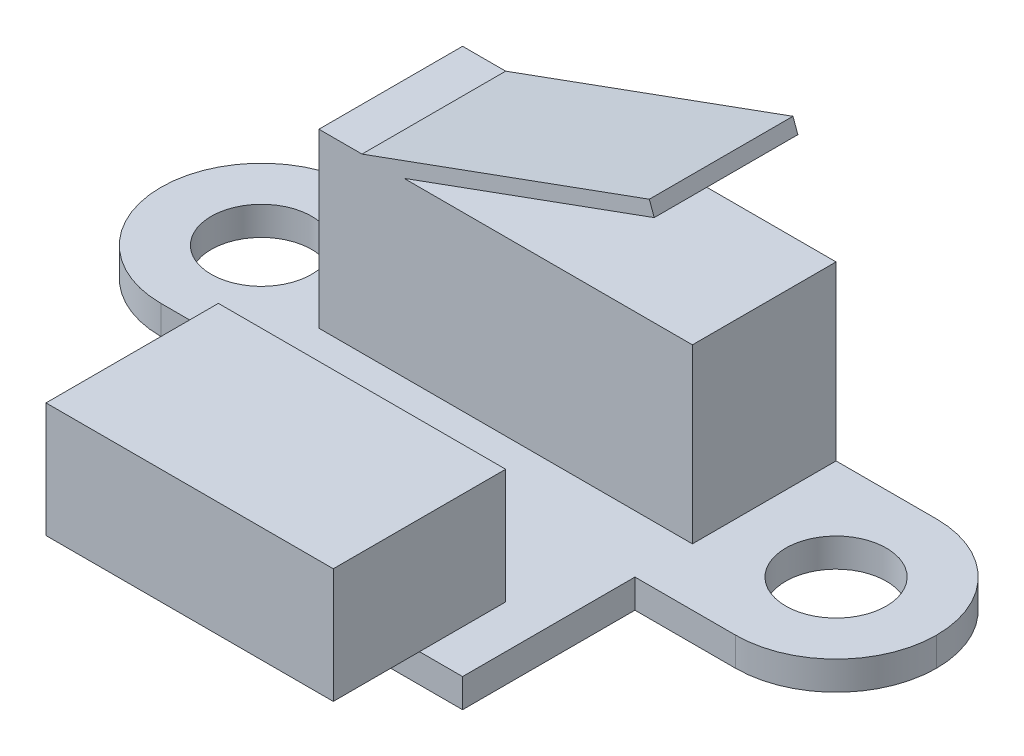
SolidWorks part; units mm, degrees
ref_plane "Front Plane" through (0, 0, 0) normal (0, 0, 1) x (1, 0, 0)
ref_plane "Top Plane" through (0, 0, 0) normal (0, 1, 0) x (1, 0, 0)
ref_plane "Right Plane" through (0, 0, 0) normal (1, 0, 0) x (0, 0, -1)
sketch "Sketch1" plane through (0, 0, 0) normal (0, 1, 0) x (1, 0, 0)
  line L1 (-6.5, -6.5) -> (6.5, -6.5)
  line L2 (-6.5, -6.5) -> (-6.5, 6.5)
  line L3 (-6.5, 6.5) -> (6.5, 6.5)
  line L4 (6.5, -6.5) -> (6.5, 6.5)
  line L5 (-6.5, -6.5) -> (6.5, 6.5) construction
  line L6 (-6.5, 6.5) -> (6.5, -6.5) construction
  point P0 (0, 0)
  dimension "D1" = 13
  dimension "D2" = 13
extrude "Boss-Extrude1" add sketch "Sketch1" along normal blind 1
sketch "Sketch4" plane through (-6.5, 0, 0) normal (-1, 0, 0) x (0, 0, 1)
  line L0 (-6.5, 1) -> (6.5, 1) construction
  line L1 (-6.5, 0) -> (0.5, 0)
  line L2 (-6.5, 0) -> (-6.5, 1)
  line L3 (-6.5, 1) -> (0.5, 1)
  line L4 (0.5, 0) -> (0.5, 1)
  dimension "D1" = 7
extrude "Boss-Extrude2" add sketch "Sketch4" along normal blind 7
sketch "Sketch5" plane through (6.5, 0, 0) normal (1, 0, 0) x (0, 0, -1)
  line L0 (-6.5, 0) -> (6.5, 0) construction
  line L1 (6.5, 1) -> (-0.5, 1)
  line L2 (6.5, 1) -> (6.5, 0)
  line L3 (6.5, 0) -> (-0.5, 0)
  line L4 (-0.5, 1) -> (-0.5, 0)
  dimension "D1" = 7
extrude "Boss-Extrude3" add sketch "Sketch5" along normal blind 7
sketch "Sketch6" plane through (0, 1, 0) normal (0, 1, 0) x (1, 0, 0)
  line L0 (-13.5, -0.5) -> (-6.5, -0.5) construction
  line L2 (-13.5, -0.5) -> (-13.5, 6.5) construction
  circle A0 centre (-10, 3) radius 1.75
  circle A1 centre (10, 3) radius 1.75
  dimension "D1" = 3.5
  dimension "D4" = 3.5
  dimension "D2" = 3.5
  dimension "D3" = 3.5
  dimension "D5" = 20
extrude "Cut-Extrude1" cut sketch "Sketch6" against normal through all
sketch "Sketch7" plane through (0, 1, 0) normal (0, 1, 0) x (1, 0, 0)
  line L0 (13.5, 6.5) -> (-13.5, 6.5) construction
  line L1 (-5, -3.5) -> (5, -3.5)
  line L2 (-5, -3.5) -> (-5, -9.5)
  line L3 (-5, -9.5) -> (5, -9.5)
  line L4 (5, -3.5) -> (5, -9.5)
  line L5 (-6.5, -0.5) -> (-6.5, -6.5) construction
  dimension "D1" = 6
  dimension "D2" = 10
  dimension "D3" = 10
  dimension "D4" = 1.5
extrude "Boss-Extrude4" add sketch "Sketch7" along normal blind 4
sketch "Sketch8" plane through (0, 1, 0) normal (0, 1, 0) x (1, 0, 0)
  line L0 (-6.5, -0.5) -> (-6.5, -6.5) construction
  line L1 (-6.5, 1.5) -> (6.5, 1.5)
  line L2 (-6.5, 1.5) -> (-6.5, 6.5)
  line L3 (-6.5, 6.5) -> (6.5, 6.5)
  line L4 (6.5, 1.5) -> (6.5, 6.5)
  line L5 (13.5, 6.5) -> (-13.5, 6.5) construction
  dimension "D1" = 13
  dimension "D2" = 0
  dimension "D3" = 5
  dimension "D4" = 0
extrude "Boss-Extrude5" add sketch "Sketch8" along normal blind 6
sketch "Sketch9" plane through (0, 0, -1.5) normal (0, 0, 1) x (1, 0, 0)
  line L0 (-5, 7) -> (5, 10.6397)
  line L1 (-6.5, 7) -> (6.5, 7) construction
  line L2 (-6.5, 7) -> (-6.5, 1) construction
  line L3 (5, 10.6397) -> (5.171, 10.1699)
  line L4 (5.171, 10.1699) -> (-3.5381, 7)
  line L5 (-3.5381, 7) -> (-5, 7)
  dimension "D1" = 10
  dimension "D2" = 1.5
  dimension "D3" = 20
  dimension "D4" = 90
  dimension "D5" = 0.5
extrude "Boss-Extrude6" add sketch "Sketch9" against normal blind 5
fillet "Fillet1" radius 3.5 4 edges at (13.5, 0.5, -6.5) (13.5, 0.5, 0.5) (-13.5, 0.5, -6.5) (-13.5, 0.5, 0.5)
